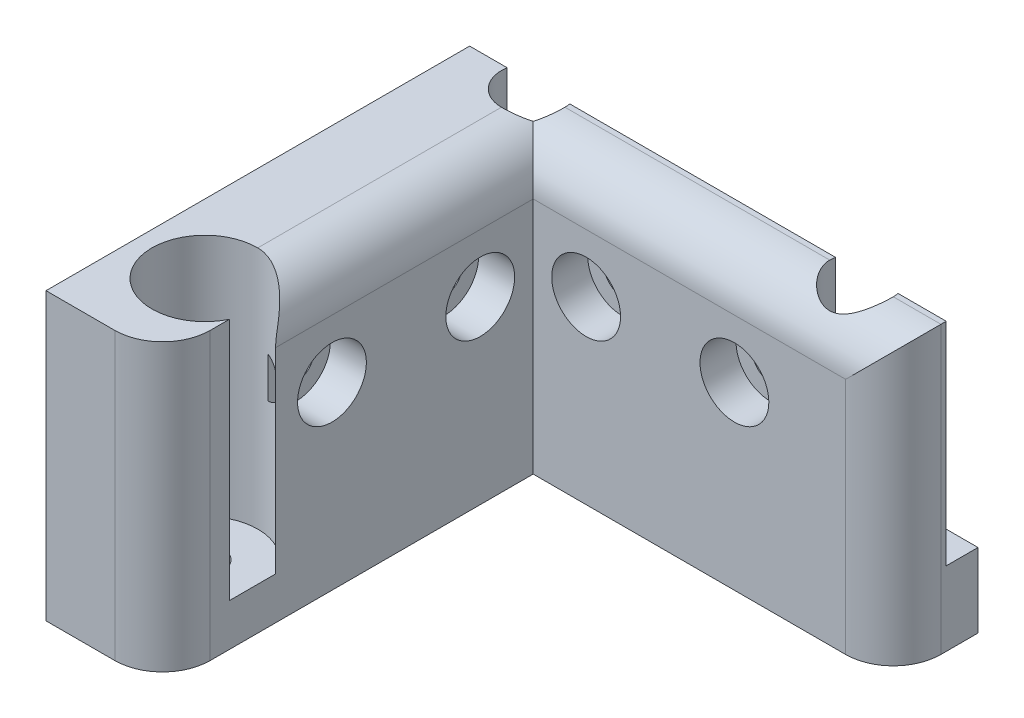
SolidWorks part; units mm, degrees
material "ABS"
ref_plane "Front Plane" through (0, 0, 0) normal (0, 0, 1) x (1, 0, 0)
ref_plane "Top Plane" through (0, 0, 0) normal (0, 1, 0) x (1, 0, 0)
ref_plane "Right Plane" through (0, 0, 0) normal (1, 0, 0) x (0, 0, -1)
sketch "Sketch1" plane through (0, 0, 0) normal (0, 1, 0) x (1, 0, 0)
  line L1 (0, 0) -> (45, 0)
  line L2 (0, 0) -> (0, 40)
  line L3 (0, 40) -> (45, 40)
  line L4 (45, 0) -> (45, 40)
  dimension "D1" = 45
  dimension "D2" = 40
extrude "Boss-Extrude1" add sketch "Sketch1" along normal blind 29
sketch "Sketch33" plane through (0, 29, 0) normal (0, 1, 0) x (1, 0, 0)
  line L0 (0, 40) -> (0, 0) construction
  line L1 (45, 0) -> (11, 0)
  line L2 (45, 0) -> (45, 35)
  line L3 (45, 35) -> (11, 35)
  line L4 (11, 0) -> (11, 35)
  line L5 (45, 40) -> (0, 40) construction
  dimension "D1" = 11
  dimension "D2" = 5
extrude "Cut-Extrude7" cut sketch "Sketch33" against normal through all
sketch "Sketch39" plane through (0, 0, -40) normal (0, 0, -1) x (-1, 0, 0)
  line L0 (0, 29) -> (0, 0) construction
  line L1 (-45, 0) -> (0, 0)
  line L2 (-45, 0) -> (-45, 9)
  line L3 (-45, 9) -> (0, 9)
  line L4 (0, 0) -> (0, 9)
  dimension "D1" = 9
extrude "Boss-Extrude2" add sketch "Sketch39" along normal blind 3
sketch "Sketch21" plane through (0, 29, 0) normal (0, 1, 0) x (1, 0, 0)
  line L0 (45, 40) -> (0, 40) construction
  circle A1 centre (6.5, 39.5) radius 1.75
  circle A2 centre (6.5, 8.5) radius 1.75
  circle A3 centre (37.5, 39.5) radius 1.75
  dimension "D3" = 0.5
  dimension "D4" = 3.5
  dimension "D7" = 3.5
  dimension "D8" = 3.5
  dimension "D1" = 0.5
  dimension "D2" = 31
extrude "Cut-Extrude6" cut sketch "Sketch21" against normal through all both and the other way through all
sketch "Sketch34" plane through (0, 29, 0) normal (0, 1, 0) x (1, 0, 0)
  circle A0 centre (6.5, 8.5) radius 5
  circle A1 centre (6.5, 39.5) radius 3
  circle A2 centre (37.5, 39.5) radius 3
  dimension "D1" = 10
  dimension "D2" = 6
  dimension "D3" = 6
extrude "Cut-Extrude8" cut sketch "Sketch34" against normal blind 23
hole_wizard "CBORE for M3 Hex Socket Head Cap Screw1" positions "Sketch35" profile "Sketch36" counterbore size "M3" standard "ISO" end condition through all
sketch "Sketch35" plane through (11, 0, 0) normal (1, 0, 0) x (0, 0, -1)
  line L1 (0, 0) -> (0, 29) construction
  line L2 (35, 0) -> (35, 29) construction
  line L3 (35, 29) -> (10.6794, 29) construction
  point P0 (16, 19)
  point P2 (30, 19)
  dimension "D1" = 10
  dimension "D2" = 10
  dimension "D3" = 16
  dimension "D4" = 5
sketch "Sketch36" plane through (11, 19, -16) normal (0, 1, 0) x (0, 0, -1)
  line L0 (0, 0) -> (0, 11)
  line L1 (0, 11) -> (1.7, 11)
  line L3 (1.7, 11) -> (1.7, 3.4)
  line L4 (1.7, 3.4) -> (3.25, 3.4)
  line L5 (3.25, 3.4) -> (3.25, 0)
  line L7 (3.25, 0) -> (0, 0)
  line L11 (0, -6.35) -> (0, 107.95) construction
  dimension "Thru Hole Dia." = 3.4
  dimension "Thru Hole Depth" = 11
  dimension "C'Bore Dia." = 6.5
  dimension "C'Bore Depth" = 3.4
hole_wizard "CBORE for M3 Hex Socket Head Cap Screw2" positions "Sketch37" profile "Sketch38" counterbore size "M3" standard "ISO" end condition through all
sketch "Sketch37" plane through (0, 0, -35) normal (0, 0, 1) x (1, 0, 0)
  line L1 (11, 0) -> (11, 29) construction
  line L2 (45, 0) -> (45, 29) construction
  line L3 (45, 29) -> (11, 29) construction
  point P0 (16, 19)
  point P2 (30, 19)
  dimension "D1" = 10
  dimension "D2" = 10
  dimension "D3" = 5
  dimension "D4" = 15
sketch "Sketch38" plane through (16, 19, -35) normal (1, 0, 0) x (0, -1, 0)
  line L0 (0, 0) -> (0, 8)
  line L1 (0, 8) -> (1.7, 8)
  line L3 (1.7, 8) -> (1.7, 3.4)
  line L4 (1.7, 3.4) -> (3.25, 3.4)
  line L5 (3.25, 3.4) -> (3.25, 0)
  line L7 (3.25, 0) -> (0, 0)
  line L11 (0, -6.35) -> (0, 107.95) construction
  dimension "Thru Hole Dia." = 3.4
  dimension "Thru Hole Depth" = 8
  dimension "C'Bore Dia." = 6.5
  dimension "C'Bore Depth" = 3.4
fillet "Fillet1" radius 4.5 5 edges at (11, 14.5, 0) (45, 14.5, -35) (28, 29, -35) (11, 29, -3.1603) (11, 29, -22.8397)
sketch "Sketch40" plane through (0, 0, 0) normal (-1, 0, 0) x (0, 0, 1)
  line L0 (-43, 0) -> (-43, 9) construction
  line L1 (-43, 2) -> (0, 2)
  line L2 (-43, 2) -> (-43, 0)
  line L3 (-43, 0) -> (0, 0)
  line L4 (0, 2) -> (0, 0)
  dimension "D1" = 2
extrude "Cut-Extrude9" cut sketch "Sketch40" against normal through all
sketch "Sketch41" plane through (0, 29, 0) normal (0, 1, 0) x (1, 0, 0)
  line L0 (3.542, 40) -> (0, 40) construction
  line L1 (0, 0) -> (6, 0)
  line L2 (0, 0) -> (0, 40)
  line L3 (0, 40) -> (6, 40)
  line L4 (6, 0) -> (6, 40)
  dimension "D1" = 6
extrude "Cut-Extrude10" [suppressed] cut sketch "Sketch41" against normal blind 20
mirror "Mirror1" [suppressed] of bodies 125 122
delete or keep bodies "Body-Delete/Keep 1" [suppressed] type delete bodies bodies 125
